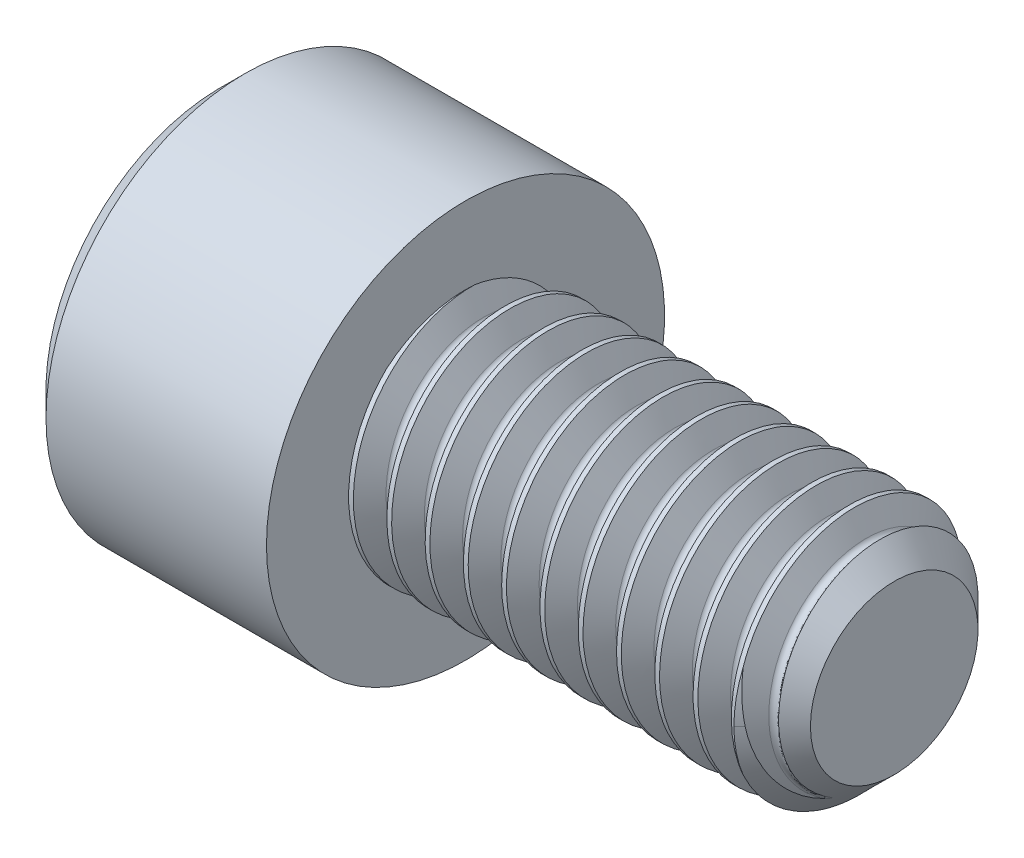
SolidWorks part; units mm, degrees
material "AISI 1020"
ref_plane "Front Plane" through (0, 0, 0) normal (0, 0, 1) x (1, 0, 0)
ref_plane "Top Plane" through (0, 0, 0) normal (0, 1, 0) x (1, 0, 0)
ref_plane "Right Plane" through (0, 0, 0) normal (1, 0, 0) x (0, 0, -1)
sketch "Sketch1" plane through (0, 0, 0) normal (0, 0, 1) x (1, 0, 0)
  line L0 (-88.7055, 0) -> (96.9812, 0) construction
  line L1 (0, 0) -> (0, 6.5)
  line L2 (0, 6.5) -> (8, 6.5)
  line L4 (22, 0) -> (22, 3.986)
  line L5 (22, 3.986) -> (8, 3.986)
  line L6 (8, 3.986) -> (8, 6.5)
  line L7 (0, 0) -> (22, 0)
revolve "Revolve1" add sketch "Sketch1" angle 360 about L0
chamfer "Chamfer1" distance 1.25 angle 45 1 edges at (22, 0, 3.986)
chamfer "Chamfer2" distance 0.8 angle 45 1 edges at (0, 0, 6.5)
sketch "Sketch3" plane through (0, 0, 0) normal (1, 0, 0) x (0, 0, -1)
  line L1 (-3.4641, 0) -> (-1.7321, -3)
  line L2 (-1.7321, -3) -> (1.7321, -3)
  line L3 (1.7321, -3) -> (3.4641, 0)
  line L4 (3.4641, 0) -> (1.7321, 3)
  line L5 (1.7321, 3) -> (-1.7321, 3)
  line L6 (-1.7321, 3) -> (-3.4641, 0)
  circle A0 centre (0, 0) radius 3 construction
  dimension "D1" = 6
extrude "Cut-Extrude1" cut sketch "Sketch3" along normal blind 5
chamfer "Chamfer3" distance 0.8 angle 45 6 edges at (0, 3, 0) (0, 1.5, 2.5981) (0, -1.5, 2.5981) (0, -3, 0) (0, -1.5, -2.5981) (0, 1.5, -2.5981)
sketch "Sketch5" plane through (22, 0, 0) normal (1, 0, 0) x (0, 0, -1)
  circle A0 centre (0, 0) radius 3.986
curve "Helix/Spiral1" pitch 1.25 height 14 radius 3.986 centre (22, 0, 0) axis (-1, 0, 0) start towards (0, 0, -1)
sketch "Sketch8" plane through (0, 0, 0) normal (0, 1, 0) x (1, 0, 0)
  line L0 (22, 3.986) -> (22, 3.0384) construction
  line L1 (22.1563, 3.3091) -> (22.8207, 4.4598)
  line L2 (22.8207, 4.4598) -> (21.1793, 4.4598)
  line L3 (21.1793, 4.4598) -> (21.8437, 3.3091)
  line L4 (22, -2.736) -> (22, 2.736) construction
  circle A0 centre (22, 3.986) radius 0.4738 construction
  arc A1 (22.1563, 3.3091) -> (21.8437, 3.3091) centre (22, 3.3994) cw
  dimension "D2" = 0.1805
  dimension "D1" = 0.9476
sweep "Cut-Sweep1" cut profiles "Sketch8" path "Helix/Spiral1" align with end faces yes
